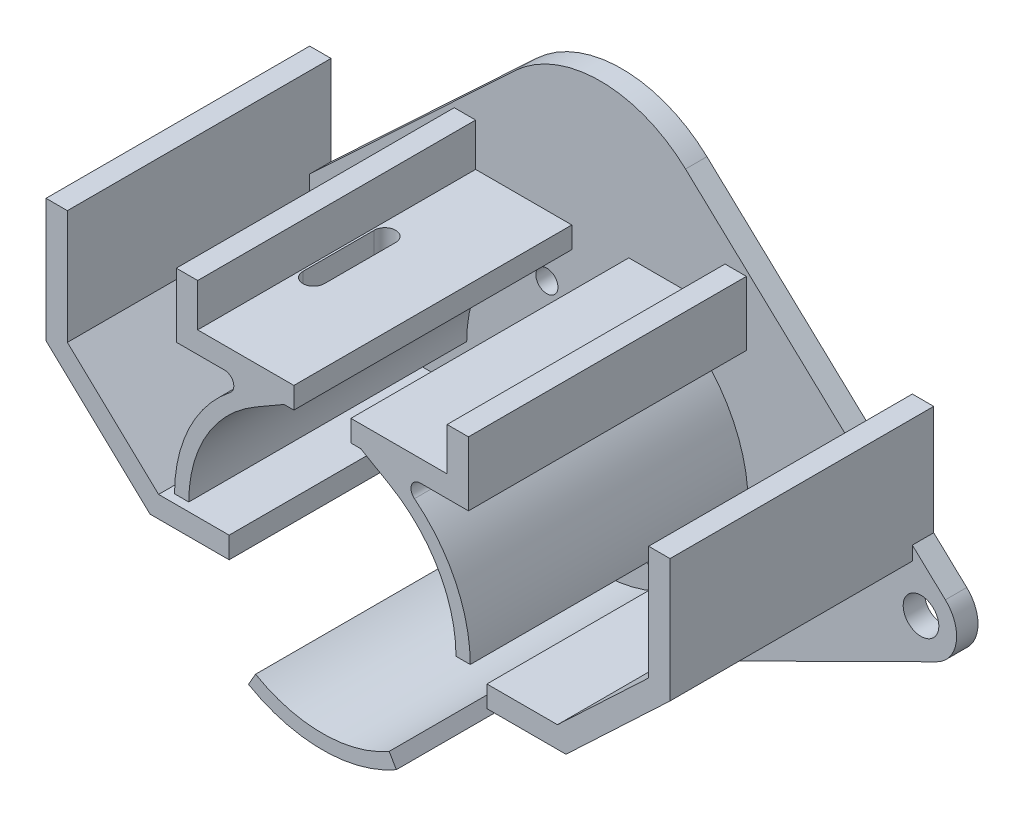
SolidWorks part; units mm, degrees
ref_plane "Front Plane" through (0, 0, 0) normal (0, 0, 1) x (1, 0, 0)
ref_plane "Top Plane" through (0, 0, 0) normal (0, 1, 0) x (1, 0, 0)
ref_plane "Right Plane" through (0, 0, 0) normal (1, 0, 0) x (0, 0, -1)
sketch "Sketch1" plane through (0, 0, 0) normal (0, 0, 1) x (1, 0, 0)
  line L0 (0, 25) -> (0, 0) construction
  line L1 (0, 1.4545) -> (-18.5, 1.4545) construction
  line L2 (-7.5, 14.4449) -> (0, 1.4545) construction
  line L3 (-7.5, -11.5359) -> (0, 1.4545) construction
  line L4 (-45, 0) -> (0, 0) construction
  line L5 (-46.6249, -4.7286) -> (-6.8247, -18.4056) construction
  line L6 (-48.4169, 3.6504) -> (-11.959, 37.7762)
  line L7 (46.6249, -4.7286) -> (6.8247, -18.4056) construction
  line L8 (48.4169, 3.6504) -> (11.959, 37.7762)
  line L9 (-16, -19.5455) -> (16, -19.5455)
  line L10 (-17.6678, -19.1542) -> (-47.2237, -4.4783)
  line L11 (17.6678, -19.1542) -> (47.2237, -4.4783)
  circle A0 centre (-25, 0) radius 2.5
  circle A1 centre (0, 1.4545) radius 18.5 construction
  circle A2 centre (0, -5.5455) radius 6.1
  circle A3 centre (0, 1.4545) radius 15 construction
  circle A4 centre (-7.5, 14.4449) radius 1.55
  circle A5 centre (-15, 1.4545) radius 1.55
  circle A6 centre (-7.5, -11.5359) radius 1.55
  circle A7 centre (-45, 0) radius 5 construction
  circle A8 centre (0, 25) radius 17.5 construction
  circle A9 centre (0, 1.4545) radius 21 construction
  arc A10 (-48.4169, 3.6504) -> (-46.6249, -4.7286) centre (-45, 0) ccw construction
  circle A11 centre (7.5, -11.5359) radius 1.55
  circle A12 centre (7.5, 14.4449) radius 1.55
  circle A13 centre (15, 1.4545) radius 1.55
  circle A14 centre (25, 0) radius 2.5
  arc A15 (48.4169, 3.6504) -> (46.6249, -4.7286) centre (45, 0) cw construction
  arc A16 (-11.959, 37.7762) -> (11.959, 37.7762) centre (0, 25) cw
  arc A17 (6.8247, -18.4056) -> (-6.8247, -18.4056) centre (0, 1.4545) cw construction
  circle A18 centre (-45, 0) radius 2.5
  circle A19 centre (45, 0) radius 2.5
  circle A20 centre (-16, -15.7955) radius 3.75 construction
  circle A21 centre (-16, -15.7955) radius 2.5
  arc A22 (-48.4169, 3.6504) -> (-47.2237, -4.4783) centre (-45, 0) ccw
  arc A23 (-17.6678, -19.1542) -> (-16, -19.5455) centre (-16, -15.7955) ccw
  circle A24 centre (16, -15.7955) radius 3.75 construction
  circle A25 centre (16, -15.7955) radius 2.5
  arc A26 (17.6678, -19.1542) -> (16, -19.5455) centre (16, -15.7955) cw
  arc A27 (48.4169, 3.6504) -> (47.2237, -4.4783) centre (45, 0) cw
  point P48 (-15.8806, -19.5455)
  point P53 (0, -19.5455)
  dimension "D1" = 5
  dimension "D2" = 50
  dimension "D3" = 37
  dimension "D5" = 12.2
  dimension "D9" = 3.1
  dimension "D10" = 30
  dimension "D12" = 10
  dimension "D13" = 35
  dimension "D15" = 42
  dimension "D16" = 5
  dimension "D17" = 7.5
  dimension "D18" = 5
  dimension "D4" = 1.4545
  dimension "D6" = 7
  dimension "D7" = 60
  dimension "D8" = 60
  dimension "D11" = 45
  dimension "D14" = 25
  dimension "D19" = 16
extrude "Boss-Extrude1" add sketch "Sketch1" along normal blind 3
sketch "Sketch2" plane through (0, 0, 3) normal (0, 0, 1) x (1, 0, 0)
  line L0 (0, 0) -> (0, 22.2045) construction
  line L1 (0, 1.4545) -> (-10.375, -16.5155) construction
  line L2 (0, 1.4545) -> (10.375, -16.5155) construction
  line L3 (0, 1.4545) -> (-20.75, 1.4545) construction
  line L4 (0, 1.4545) -> (-10.375, 19.4245) construction
  line L5 (-10.375, 19.4245) -> (-9.375, 17.6925)
  line L6 (-20.75, 1.4545) -> (-18.75, 1.4545)
  line L7 (-10.375, -16.5155) -> (-9.375, -14.7835)
  line L8 (10.375, -16.5155) -> (9.375, -14.7835)
  line L9 (10.375, 19.4245) -> (9.375, 17.6925)
  line L10 (20.75, 1.4545) -> (18.75, 1.4545)
  circle A0 centre (0, 1.4545) radius 18.5 construction
  circle A1 centre (0, 1.4545) radius 18.5 construction
  circle A2 centre (0, 1.4545) radius 18.75 construction
  circle A3 centre (0, 1.4545) radius 20.75 construction
  arc A4 (-20.75, 1.4545) -> (-10.375, 19.4245) centre (0, 1.4545) cw
  arc A5 (-18.75, 1.4545) -> (-9.375, 17.6925) centre (0, 1.4545) cw
  arc A6 (-9.375, -14.7835) -> (9.375, -14.7835) centre (0, 1.4545) ccw
  arc A7 (-10.375, -16.5155) -> (10.375, -16.5155) centre (0, 1.4545) ccw
  arc A8 (20.75, 1.4545) -> (10.375, 19.4245) centre (0, 1.4545) ccw
  arc A9 (18.75, 1.4545) -> (9.375, 17.6925) centre (0, 1.4545) ccw
  dimension "D1" = 37.5
  dimension "D2" = 2
  dimension "D3" = 150
  dimension "D4" = 150
  dimension "D5" = 60
  dimension "D6" = 60
extrude "Boss-Extrude2" add sketch "Sketch2" along normal blind 39 contours L6 A5 L5 A4 | L7 A7 L8 A6 | A9 L10 A8 L9 region at (-16.3471, 10.8925, 3) region at (0, -17.4215, 3) region at (16.3471, 10.8925, 3)
sketch "Sketch3" plane through (0, 0, 3) normal (0, 0, 1) x (1, 0, 0)
  line L0 (0, 0) -> (0, 23) construction
  line L1 (-12.5, 38) -> (12.5, 38) construction
  line L2 (-12.5, 38) -> (-12.5, 23) construction
  line L3 (-12.5, 23) -> (12.5, 23) construction
  line L4 (12.5, 38) -> (12.5, 23) construction
  line L5 (0, 25) -> (0, 0) construction
  line L6 (-17.5, 29) -> (-17.5, 23)
  line L7 (-17.5, 23) -> (-4, 23)
  line L8 (-4, 23) -> (-4, 20)
  line L9 (-4, 20) -> (-5.3783, 20)
  line L10 (-17.5, 29) -> (-20.5, 29)
  line L11 (-20.5, 29) -> (-20.5, 20)
  line L12 (-20.5, 20) -> (-13.7246, 20)
  line L13 (-9.375, 17.6925) -> (-5.3783, 20)
  line L14 (-12.9186, 17.6925) -> (-9.375, 17.6925)
  arc A0 (-9.375, 17.6925) -> (-18.75, 1.4545) centre (0, 1.4545) ccw construction
  arc A1 (-13.7246, 20) -> (-12.9186, 17.6925) centre (-13.7246, 18.7055) cw
  arc A2 (-10.375, 19.4245) -> (-20.75, 1.4545) centre (0, 1.4545) ccw construction
  dimension "D1" = 25
  dimension "D2" = 15
  dimension "D3" = 23
  dimension "D4" = 8
  dimension "D5" = 3
  dimension "D6" = 35
  dimension "D7" = 3
  dimension "D8" = 6
extrude "Boss-Extrude3" add sketch "Sketch3" along normal up to surface (39 mm away) up to face at (-15.9583, 10.668, 42)
mirror "Mirror1" about plane through (0, 0, 0) normal (1, 0, 0) of "Boss-Extrude3"
sketch "Sketch4" plane through (0, 23, 0) normal (0, 1, 0) x (1, 0, 0)
  line L0 (-13.7246, -42) -> (-13.7246, -3) construction
  line L1 (-13.7246, -42) -> (-13.7246, -3) construction
  line L2 (-15.7246, -17.5) -> (-15.7246, -27.5) construction
  line L3 (-14.2246, -17.5) -> (-14.2246, -27.5)
  line L4 (-17.2246, -17.5) -> (-17.2246, -27.5)
  line L5 (-15.7246, -22.5) -> (-13.7246, -22.5) construction
  line L6 (0, 0) -> (0, -40.251) construction
  line L7 (15.7246, -17.5) -> (15.7246, -27.5) construction
  line L8 (14.2246, -17.5) -> (14.2246, -27.5)
  line L9 (17.2246, -17.5) -> (17.2246, -27.5)
  arc A0 (-14.2246, -17.5) -> (-17.2246, -17.5) centre (-15.7246, -17.5) ccw
  arc A1 (-17.2246, -27.5) -> (-14.2246, -27.5) centre (-15.7246, -27.5) ccw
  arc A2 (14.2246, -17.5) -> (17.2246, -17.5) centre (15.7246, -17.5) cw
  arc A3 (17.2246, -27.5) -> (14.2246, -27.5) centre (15.7246, -27.5) cw
  point P4 (-15.7246, -22.5)
  point P16 (15.7246, -22.5)
  dimension "D1" = 3
  dimension "D2" = 2
  dimension "D3" = 10
extrude "Cut-Extrude1" cut sketch "Sketch4" against normal up to surface (3 mm away) up to face at (-17.1123, 20, 22.5)
sketch "Sketch5" plane through (0, 0, 3) normal (0, 0, 1) x (1, 0, 0)
  line L0 (-43.7844, 23.3468) -> (-43.7844, 6.0404)
  line L1 (-43.7844, 6.0404) -> (-29.1766, -7.7395)
  line L2 (-27.9848, -4.7395) -> (-40.7844, 7.3346)
  line L3 (-40.7844, 7.3346) -> (-40.7844, 23.3468)
  line L4 (-43.7844, 23.3468) -> (-40.7844, 23.3468)
  line L6 (-27.9848, -4.7395) -> (-18.0861, -4.7395)
  line L7 (-29.1766, -7.7395) -> (-18.0861, -7.7395)
  line L8 (-18.0861, -7.7395) -> (-18.0861, -4.7395)
  point P2 (-29.1506, -7.764)
  point P7 (-18.0861, -7.7395)
  dimension "D1" = 3
  dimension "D2" = 3
  dimension "D3" = 3
extrude "Boss-Extrude4" add sketch "Sketch5" along normal blind 34
mirror "Mirror2" about plane through (0, 0, 0) normal (1, 0, 0) of "Boss-Extrude4"
sketch "Sketch6" plane through (0, 0, 3) normal (0, 0, -1) x (-1, 0, 0)
  line L4 (40.7844, 23.3468) -> (40.7844, 10.7946)
  line L5 (40.7844, 10.7946) -> (43.7844, 7.9865)
  line L6 (43.7844, 7.9865) -> (43.7844, 23.3468)
  line L7 (43.7844, 23.3468) -> (40.7844, 23.3468)
  line L8 (40.7844, 23.3468) -> (40.7844, 10.7946)
  line L9 (40.7844, 10.7946) -> (43.7844, 7.9865)
  line L10 (43.7844, 7.9865) -> (43.7844, 23.3468)
  line L11 (43.7844, 23.3468) -> (40.7844, 23.3468)
  line L12 (-43.7844, 23.3468) -> (-43.7844, 7.9865)
  line L13 (-43.7844, 7.9865) -> (-40.7844, 10.7946)
  line L14 (-40.7844, 10.7946) -> (-40.7844, 23.3468)
  line L15 (-40.7844, 23.3468) -> (-43.7844, 23.3468)
  line L16 (-43.7844, 23.3468) -> (-43.7844, 7.9865)
  line L17 (-43.7844, 7.9865) -> (-40.7844, 10.7946)
  line L18 (-40.7844, 10.7946) -> (-40.7844, 23.3468)
  line L19 (-40.7844, 23.3468) -> (-43.7844, 23.3468)
  dimension "D1" = 0
  dimension "D2" = 0
extrude "Boss-Extrude5" add sketch "Sketch6" along normal up to surface (3 mm away) up to face at (0, 0.0404, 0)
sketch "Sketch7" plane through (0, 0, 3) normal (0, 0, 1) x (1, 0, 0)
  circle A0 centre (-18.7282, -11.5671) radius 3.75 construction
  circle A1 centre (-18.7282, -11.5671) radius 2.5
  point P3 (-18.7282, -11.5671)
  dimension "D1" = 7.5
  dimension "D2" = 5
equation "\"D4@Sketch2\"=\"D3@Sketch2\""
